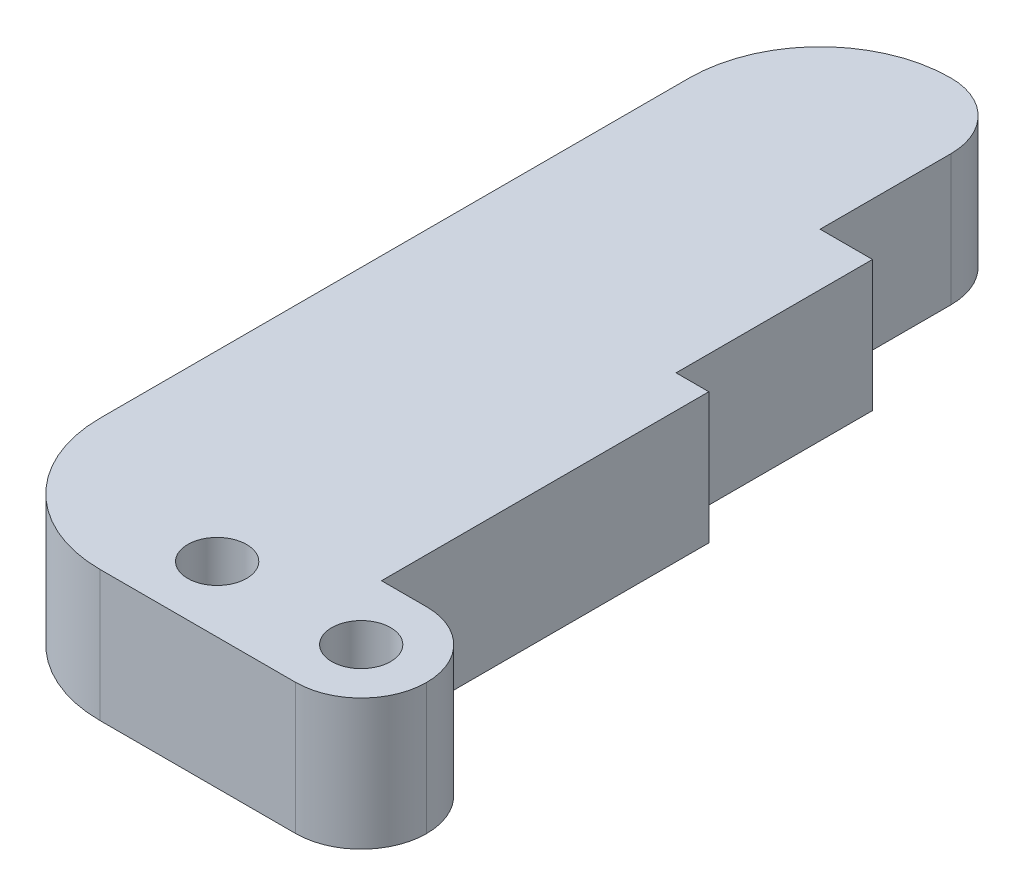
SolidWorks part; units mm, degrees
ref_plane "Front Plane" through (0, 0, 0) normal (0, 0, 1) x (1, 0, 0)
ref_plane "Top Plane" through (0, 0, 0) normal (0, 1, 0) x (1, 0, 0)
ref_plane "Right Plane" through (0, 0, 0) normal (1, 0, 0) x (0, 0, -1)
sketch "Sketch1" plane through (0, 0, 0) normal (0, 1, 0) x (1, 0, 0)
  line L0 (-100, 0) -> (100, 0) construction
  line L1 (0, -100) -> (0, 100) construction
  line L3 (8.5, 4.9075) -> (8.5, 14.7224) construction
  line L4 (8.5, 14.7224) -> (0, 19.6299) construction
  line L5 (0, 19.6299) -> (-8.5, 14.7224) construction
  line L6 (-8.5, 14.7224) -> (-8.5, 4.9075) construction
  line L7 (-8.5, 4.9075) -> (0, 0) construction
  line L8 (0, 0) -> (8.5, 4.9075) construction
  line L9 (11, 17.4641) -> (11, 30.1658) construction
  line L10 (11, 30.1658) -> (0, 36.5167) construction
  line L11 (0, 36.5167) -> (-11, 30.1658) construction
  line L12 (-11, 30.1658) -> (-11, 17.4641) construction
  line L13 (-11, 17.4641) -> (0, 11.1132) construction
  line L14 (0, 11.1132) -> (11, 17.4641) construction
  line L15 (15, 50.4752) -> (0, 59.1355) construction
  line L16 (0, 59.1355) -> (-15, 50.4752) construction
  line L17 (-15, 50.4752) -> (-15, 33.1547) construction
  line L18 (-15, 33.1547) -> (0, 24.4944) construction
  line L19 (0, 24.4944) -> (15, 33.1547) construction
  line L20 (15, 33.1547) -> (15, 50.4752) construction
  circle A0 centre (0, 9.815) radius 8.5 construction
  circle A1 centre (0, 23.815) radius 11 construction
  circle A2 centre (0, 41.815) radius 15 construction
  point P4 (0, 0)
  point P8 (0, 0)
  dimension "D2" = 17
  dimension "D4" = 22
  dimension "D6" = 30
  dimension "D1" = 200
  dimension "D3" = 14
  dimension "D5" = 18
sketch "Sketch2" plane through (0, 0, 0) normal (0, 1, 0) x (1, 0, 0)
  line L1 (0, -100) -> (0, 100) construction
  line L3 (-100, 0) -> (100, 0) construction
  line L5 (-8.45, 15) -> (-10.95, 15)
  line L6 (-10.95, 15) -> (-10.95, 30)
  line L7 (-10.95, 30) -> (-14.95, 30)
  line L8 (-14.95, 30) -> (-14.95, 45)
  line L9 (-14.95, 45) -> (-29.95, 45)
  line L11 (0, -20) -> (-29.95, -20)
  line L12 (-29.95, -20) -> (-29.95, 45)
  line L13 (0, -20) -> (0, -10)
  line L14 (0, -10) -> (-8.45, -10)
  line L15 (-8.45, 15) -> (-8.45, -10)
  point P0 (-8.4305, 34.5743)
  point P1 (0, 23.2647)
  point P4 (0, 23.8218)
  dimension "D1" = 8.45
  dimension "D5" = 10.95
  dimension "D7" = 14.95
  dimension "D2" = 10
  dimension "D3" = 15
  dimension "D4" = 65
  dimension "D6" = 15
extrude "Boss-Extrude1" add sketch "Sketch2" along normal blind 10
sketch "Sketch3" plane through (0, 10, 0) normal (0, 1, 0) x (1, 0, 0)
  line L0 (-16, -15) -> (-5, -15) construction
  line L1 (0, -20) -> (0, -10) construction
  circle A0 centre (-5, -15) radius 2.25
  circle A1 centre (-16, -15) radius 2.25
  point P6 (0, -15)
  dimension "D2" = 4.5
  dimension "D1" = 11
  dimension "D3" = 5
extrude "Cut-Extrude1" cut sketch "Sketch3" against normal blind 10
fillet "Fillet1" radius 10 2 edges at (-29.95, 5, 20) (-29.95, 5, -45)
fillet "Fillet2" radius 5 3 edges at (-14.95, 5, -45) (0, 5, 10) (0, 5, 20)
